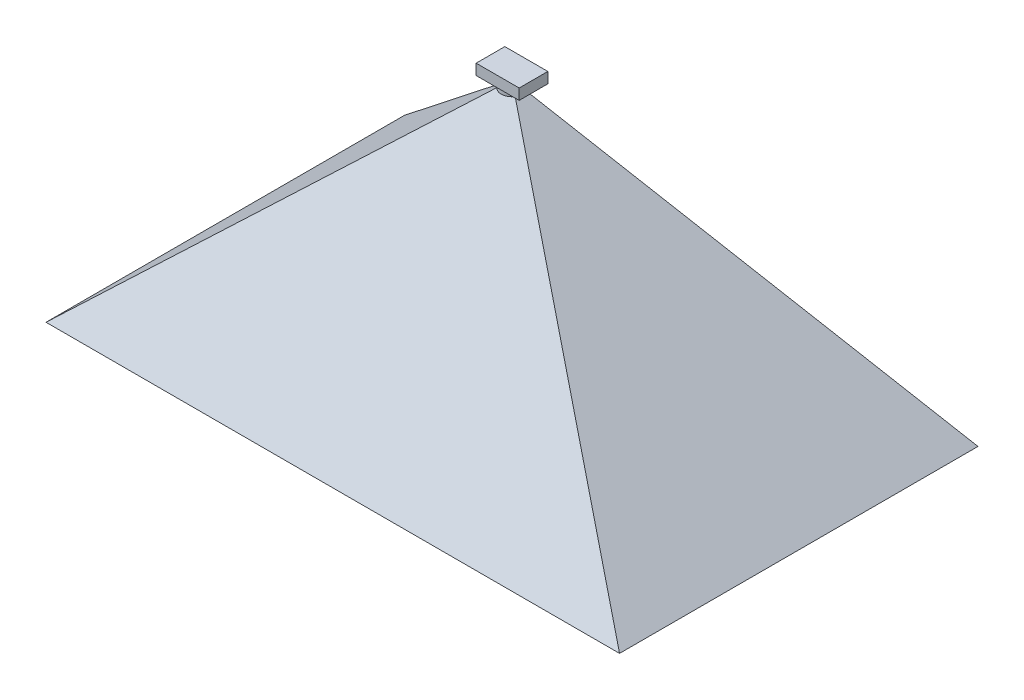
SolidWorks part; units mm, degrees
ref_plane "Front Plane" through (0, 0, 0) normal (0, 0, 1) x (1, 0, 0)
ref_plane "Top Plane" through (0, 0, 0) normal (0, 1, 0) x (1, 0, 0)
ref_plane "Right Plane" through (0, 0, 0) normal (1, 0, 0) x (0, 0, -1)
ref_plane "distance of measurement" through (0, 90.932, 0) normal (0, 1, 0) x (1, 0, 0)
sketch "Sketch1" plane through (0, 0, 0) normal (0, 1, 0) x (1, 0, 0)
  line L1 (-101.6, -63.5) -> (101.6, -63.5)
  line L2 (-101.6, -63.5) -> (-101.6, 63.5)
  line L3 (-101.6, 63.5) -> (101.6, 63.5)
  line L4 (101.6, -63.5) -> (101.6, 63.5)
  line L5 (-101.6, -63.5) -> (101.6, 63.5) construction
  line L6 (-101.6, 63.5) -> (101.6, -63.5) construction
  point P0 (0, 0)
sketch "Sketch2" plane through (0, 90.932, 0) normal (0, 1, 0) x (1, 0, 0)
  line L0 (-101.6, -63.5) -> (101.6, 63.5) construction
  line L1 (-2.7554, -1.7221) -> (2.7554, -1.7221)
  line L2 (-2.7554, -1.7221) -> (-2.7554, 1.7221)
  line L3 (-2.7554, 1.7221) -> (2.7554, 1.7221)
  line L4 (2.7554, -1.7221) -> (2.7554, 1.7221)
  line L5 (-2.7554, -1.7221) -> (2.7554, 1.7221) construction
  line L6 (-2.7554, 1.7221) -> (2.7554, -1.7221) construction
  point P0 (0, 0)
loft "FOV" add profiles "Sketch2", "Sketch1" connector at (-2.7554, 90.932, 1.7221) connector at (-101.6, 0, 63.5)
sketch "Sketch3" plane through (0, 90.932, 0) normal (0, 1, 0) x (1, 0, 0)
  circle A0 centre (0, 0) radius 3.81
extrude "camera lens" add sketch "Sketch3" along normal blind 2.54
sketch "Sketch4" plane through (0, 93.472, 0) normal (0, 1, 0) x (1, 0, 0)
  line L1 (7.62, -5.08) -> (-7.62, -5.08)
  line L2 (7.62, -5.08) -> (7.62, 5.08)
  line L3 (7.62, 5.08) -> (-7.62, 5.08)
  line L4 (-7.62, -5.08) -> (-7.62, 5.08)
  line L5 (7.62, -5.08) -> (-7.62, 5.08) construction
  line L6 (7.62, 5.08) -> (-7.62, -5.08) construction
  point P0 (0, 0)
  dimension "D1" = 15.24
  dimension "D2" = 10.16
extrude "camera holder" add sketch "Sketch4" along normal blind 3.81
ref_point "centre of vision"
